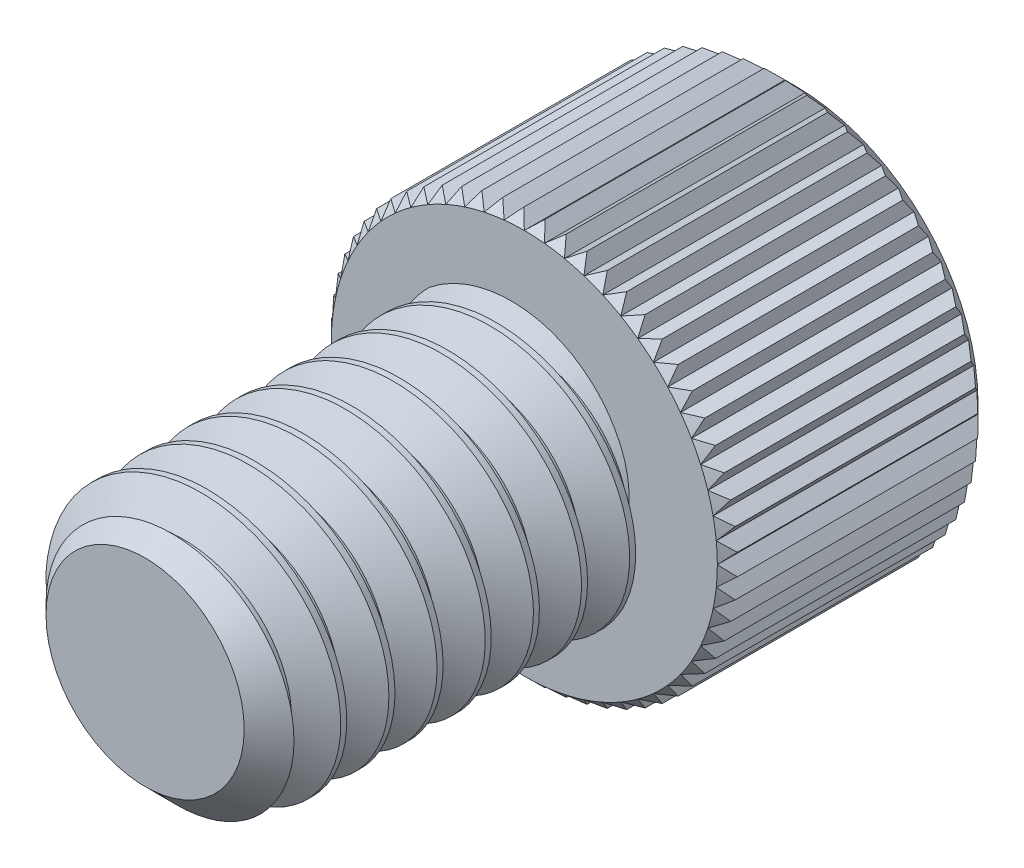
SolidWorks part; units mm, degrees
note: '?' marks a value the reader was unsure of.
ref_plane "Front Plane" through (0, 0, 0) normal (0, 0, 1) x (1, 0, 0)
ref_plane "Top Plane" through (0, 0, 0) normal (0, 1, 0) x (1, 0, 0)
ref_plane "Right Plane" through (0, 0, 0) normal (1, 0, 0) x (0, 0, -1)
sketch "Sketch0" plane through (0, 0, 0) normal (1, 0, 0) x (0, 0, -1)
  line L0 (0, 0) -> (11.1125, 0) construction
  point P2 (19.05, 0)
  point P4 (0, 0)
  point P5 (19.05, 0)
  point P6 (0, 0)
  dimension "D1" = 11.1125
  dimension "D2" = 7.9375
  dimension "Min Thread" = 0
sketch "Sketch1" plane through (0, 0, 0) normal (0, 0, 1) x (1, 0, 0)
  circle A0 centre (0, 0) radius 3.9624
  dimension "OD" = 7.9248
extrude "Extrude1" add sketch "Sketch1" against normal blind 11.1125
sketch "Sketch2" plane through (0, 0, 0) normal (0, 0, 1) x (1, 0, 0)
  circle A0 centre (0, 0) radius 3.9624 construction
  circle A1 centre (0, 0) radius 3.9624
curve "Helix/Spiral1" pitch 1.4111 height 12.5236 turns 8.875 parameters "pitch"=1.4111
chamfer "Chamfer3" distance 1.0583 angle 45 1 edges at (3.9624, 0, 0)
sketch "Sketch3" plane through (0, 0, 0) normal (1, 0, 0) x (0, 0, -1)
  line L0 (-1.2347, 3.9624) -> (-0.7056, 3.0459)
  line L1 (-0.7056, 3.0459) -> (-0.5292, 3.0459)
  line L2 (-0.5292, 3.0459) -> (0, 3.9624)
  line L3 (-1.2347, 3.9624) -> (0, 3.9624)
  line L4 (-0.6174, 3.9624) -> (-0.6174, 3.0459) construction
  line L5 (-0.9701, 3.5041) -> (-0.2646, 3.5041) construction
  line L6 (0, 3.9624) -> (0, -3.9624) construction
  dimension "D1" = 0.1764
  dimension "D2" = 0.7056
  dimension "D3" = 60
sweep "Cut-Sweep1" cut profiles "Sketch3" path "Helix/Spiral1"
sketch "Sketch5" plane through (0, 0, 0) normal (1, 0, 0) x (0, 0, -1)
  line L0 (11.1125, -3.3708) -> (11.1125, 0) construction
  line L1 (11.1125, 3.9624) -> (0, 3.9624)
  line L2 (11.1125, 3.9624) -> (11.1125, 0)
  line L3 (11.1125, 0) -> (-1.4422, 0)
  line L4 (0, 0) -> (11.1125, 0) construction
  line L5 (0, 3.9624) -> (-1.4422, 0)
  line L6 (0, 0) -> (13.6525, 0) construction
  dimension "D1" = 70
  dimension "D3" = 2.54
revolve "partially thread" [suppressed] add sketch "Sketch5" angle 360 about L6
sketch "Sketch6" plane through (0, 0, -11.1125) normal (0, 0, -1) x (-1, 0, 0)
  circle A0 centre (0, 0) radius 5.9531
  dimension "head dia" = 11.9062
extrude "Extrude2" add sketch "Sketch6" along normal blind 7.9375
sketch "Sketch7" plane through (0, 0, -19.05) normal (0, 0, -1) x (-1, 0, 0)
  line L1 (0, 3.6662) -> (-3.175, 1.8331)
  line L2 (-3.175, 1.8331) -> (-3.175, -1.8331)
  line L3 (-3.175, -1.8331) -> (0, -3.6662)
  line L4 (0, -3.6662) -> (3.175, -1.8331)
  line L5 (3.175, -1.8331) -> (3.175, 1.8331)
  line L6 (3.175, 1.8331) -> (0, 3.6662)
  circle A0 centre (0, 0) radius 3.175 construction
  dimension "hex dia" = 6.35
extrude "Cut-Extrude1" cut sketch "Sketch7" against normal blind 4.7625
sketch "Sketch8" plane through (0, 0, -19.05) normal (0, 0, -1) x (-1, 0, 0)
  circle A0 centre (0, 0) radius 3.6662
extrude "Cut-Extrude2" cut sketch "Sketch8" against normal through all draft 45
chamfer "Chamfer1" distance 0.5953 angle 45 1 edges at (-5.9531, 0, -19.05)
chamfer "Chamfer2" distance 0.2977 angle 45 1 edges at (-5.9531, 0, -11.1125)
sketch "Sketch9" plane through (0, 0, 0) normal (1, 0, 0) x (0, 0, -1)
  line L0 (0, 3.9624) -> (0, -3.9624) construction
  line L1 (3.5278, 3.9624) -> (3.5278, -3.9624) construction
  line L2 (19.05, 5.9531) -> (19.05, -5.9531) construction
  line L3 (11.1125, 5.9531) -> (11.1125, -5.9531) construction
  line L4 (11.1125, 5.6555) -> (11.1125, -5.6555) construction
  line L5 (19.05, -5.3578) -> (19.05, 5.3578) construction
  line L6 (11.1125, -5.9531) -> (11.1125, 5.9531) construction
  line L7 (0, 2.9041) -> (0, -2.9041) construction
  line L8 (-1.2347, 3.9624) -> (0, 3.9624) construction
  line L9 (3.5278, 0) -> (0, 0) construction
  dimension "D1" = 3.5278
sketch "Sketch10" plane through (0, 0, -11.1125) normal (0, 0, 1) x (1, 0, 0)
  line L0 (-0.6407, 6.2508) -> (0, 5.6555)
  line L1 (0, 5.6555) -> (0.6407, 6.2508)
  line L2 (0, 5.6555) -> (0, 6.2508) construction
  line L3 (-0.6407, 6.2508) -> (0.6407, 6.2508)
  line L4 (0, -6.5395) -> (0, 6.5395) construction
  line L5 (0, 0) -> (0.3116, 5.945) construction
  line L6 (-0.3116, 5.945) -> (0, 0) construction
  circle A2 centre (0, 0) radius 5.9531 construction
  circle A5 centre (0, 0) radius 5.6555 construction
  dimension "D1" = 6
  dimension "D2" = 0.5953
extrude "Cut-Extrude3" cut sketch "Sketch10" against normal through all
pattern_circular "CirPattern1" count 60 over 360 about axis through (0, 0, 0) along (0, 0, 1) of "Cut-Extrude3"
ref_plane "Contact Plane 1" through (0, 0, -11.1125) normal (0, 0, 1) x (1, 0, 0)
ref_axis "Center Axis 1" through (0, 0, 1.3957) along (0, 0, -1)?
equation "\"D3@Helix/Spiral1\" = \"screw length@Extrude1\"+\"pitch@Helix/Spiral1\""
equation "\"D1@Sketch3\" = \"pitch@Helix/Spiral1\"*.125"
equation "\"D2@Sketch3\" = \"pitch@Helix/Spiral1\"*.5"
equation "\"D1@Cut-Extrude1\" = \"hex dia@Sketch7\"*.75"
equation "\"D1@Chamfer1\" = \"head dia@Sketch6\"*.05"
equation "\"D1@Sketch9\" = \"pitch@Helix/Spiral1\"*2.50"
equation "\"D1@Chamfer2\" = \"D1@Chamfer1\"/2"
equation "\"D1@Chamfer3\" = \"pitch@Helix/Spiral1\"*.750"
equation "\"D1@Sketch0\" = \"screw length@Extrude1\""
equation "\"D2@Sketch0\" = \"head depth@Extrude2\""
equation "\"D2@Sketch10\"=\"D1@Chamfer1\""
equation "\"D1@CirPattern1\"=\"D3@CirPattern1\"/\"D1@Sketch10\""
